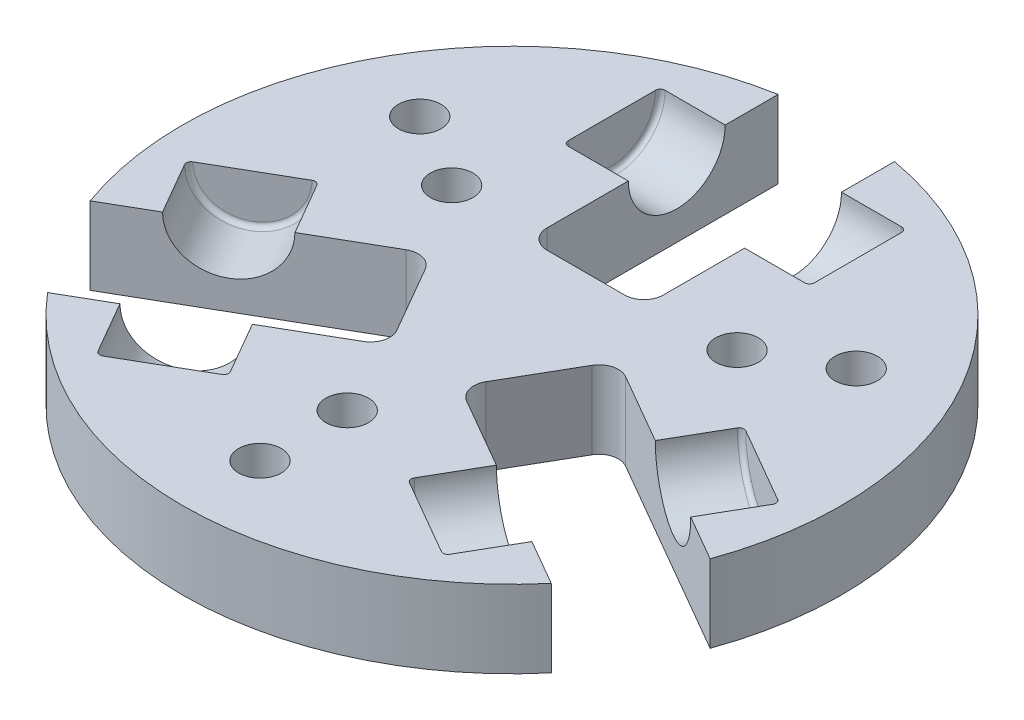
SolidWorks part; units mm, degrees
material "7075-T6 (SN)"
ref_plane "Front" through (0, 0, 0) normal (0, 0, 1) x (1, 0, 0)
ref_plane "Top" through (0, 0, 0) normal (0, 1, 0) x (1, 0, 0)
ref_plane "Right" through (0, 0, 0) normal (1, 0, 0) x (0, 0, -1)
sketch "Sketch1" plane through (0, 0, 0) normal (0, 1, 0) x (1, 0, 0)
  line L0 (0, 0) -> (0, 16) construction
  line L1 (0, 0) -> (-13.8564, -8) construction
  line L2 (0, 0) -> (13.8564, -8) construction
  line L3 (-12.7, 7.3323) -> (-12.7, 16) construction
  line L4 (-12.7, 16) -> (12.7, 16) construction
  line L5 (12.7, 16) -> (12.7, 7.3323) construction
  line L6 (-20.2064, 2.9985) -> (-12.7, 7.3323) construction
  line L7 (-20.2064, 2.9985) -> (-7.5064, -18.9985) construction
  line L8 (-7.5064, -18.9985) -> (0, -14.6647) construction
  line L9 (0, -14.6647) -> (7.5064, -18.9985) construction
  line L10 (7.5064, -18.9985) -> (20.2064, 2.9985) construction
  line L11 (20.2064, 2.9985) -> (12.7, 7.3323) construction
  line L12 (-20.2064, 2.9985) -> (-12.7, 16) construction
  line L13 (12.7, 16) -> (20.2064, 2.9985) construction
  line L14 (7.5064, -18.9985) -> (-7.5064, -18.9985) construction
  circle A0 centre (0, 0) radius 12.7 construction
  circle A1 centre (0, 0) radius 17
  dimension "D4" = 25.4
  dimension "D5" = 34
  dimension "D1" = 120
  dimension "D2" = 120
  dimension "D3" = 16
extrude "Boss-Extrude1" add sketch "Sketch1" along normal blind 8
ref_axis "Axis1" through (0, 40.005, 0) along (0, -1, 0)
sketch "Sketch9" plane through (0, 8, 0) normal (0, 1, 0) x (1, 0, 0)
  line L0 (0, 0) -> (0, 3.81) construction
  line L2 (-3, 17) -> (3, 17)
  line L3 (3, 17) -> (3, 3.81)
  line L4 (3, 3.81) -> (-3, 3.81)
  line L5 (-3, 3.81) -> (-3, 17)
  circle A0 centre (0, 0) radius 17 construction
  dimension "D1" = 6
  dimension "D3" = 3.81
extrude "Cut-Extrude1" cut sketch "Sketch9" against normal through all contours L5 L2 L3 L4
sketch "Sketch10" plane through (0, 0, 0) normal (1, 0, 0) x (0, 0, -1)
  line L5 (11.5, 8) -> (11.5, 0) construction
  line L11 (-17, 0) -> (16.7332, 0) construction
  line L12 (16.7332, 8) -> (3.81, 8) construction
  circle A0 centre (11.5, 4) radius 2.5
  dimension "D1" = 5
  dimension "D2" = 11.5
extrude "Cut-Extrude2" cut sketch "Sketch10" against normal mid plane 12.7
fillet "Fillet2" radius 1 2 edges at (3, 4, -3.81) (-3, 4, -3.81)
pattern_circular "CirPattern2" count 3 over 360 about axis through (0, 40.005, 0) along (0, -1, 0) of "Cut-Extrude1", "Cut-Extrude2", "Fillet2"
ref_plane "Plane1" through (0, 4, 0) normal (0, 1, 0) x (1, 0, 0)
sketch "Sketch12" plane through (0, 4, 0) normal (0, 1, 0) x (1, 0, 0)
  circle A0 centre (0, 0) radius 20
  dimension "D1" = 40
extrude "Cut-Extrude3" cut sketch "Sketch12" along normal blind 10 contours A0
hole_wizard "Ø2.2 (2.2) Diameter Hole1" positions "Sketch19" profile "Sketch18" hole size "Ø2.2" standard "ANSI Metric" end condition through all
sketch "Sketch19" plane through (0, 0, 0) normal (0, 1, 0) x (1, 0, 0)
  line L0 (-11.2583, 6.5) -> (0, 0) construction
  line L1 (0, 0) -> (11.2583, 6.5) construction
  line L3 (0, -13) -> (0, 0) construction
  circle A0 centre (0, 0) radius 8.5
  circle A1 centre (0, 0) radius 13
  point P0 (-11.2583, 6.5)
  point P3 (11.2583, 6.5)
  point P5 (0, -13)
  point P29 (-7.3612, 4.25)
  point P31 (7.3612, 4.25)
  point P33 (0, -8.5)
  dimension "D1" = 17
  dimension "D4" = 26
  dimension "D2" = 120
  dimension "D3" = 120
sketch "Sketch18" plane through (-11.2583, 0, -6.5) normal (1, 0, 0) x (0, 0, -1)
  line L0 (0, 0) -> (0, 4)
  line L1 (0, 4) -> (1.1, 4)
  line L2 (1.1, 4) -> (1.1, 0)
  line L5 (1.1, 0) -> (0, 0)
  line L11 (0, -6.35) -> (0, 107.95) construction
  dimension "Thru Hole Dia." = 2.2
  dimension "Thru Hole Depth" = 4
fillet "Fillet3" radius 0.25 6 edges at (-13.1343, 1.5, 0.2507) (-6.7843, 1.5, 11.2493) (6.7843, 1.5, 11.2493) (13.1343, 1.5, 0.2507) (-6.35, 1.5, -11.5) (6.35, 1.5, -11.5)
